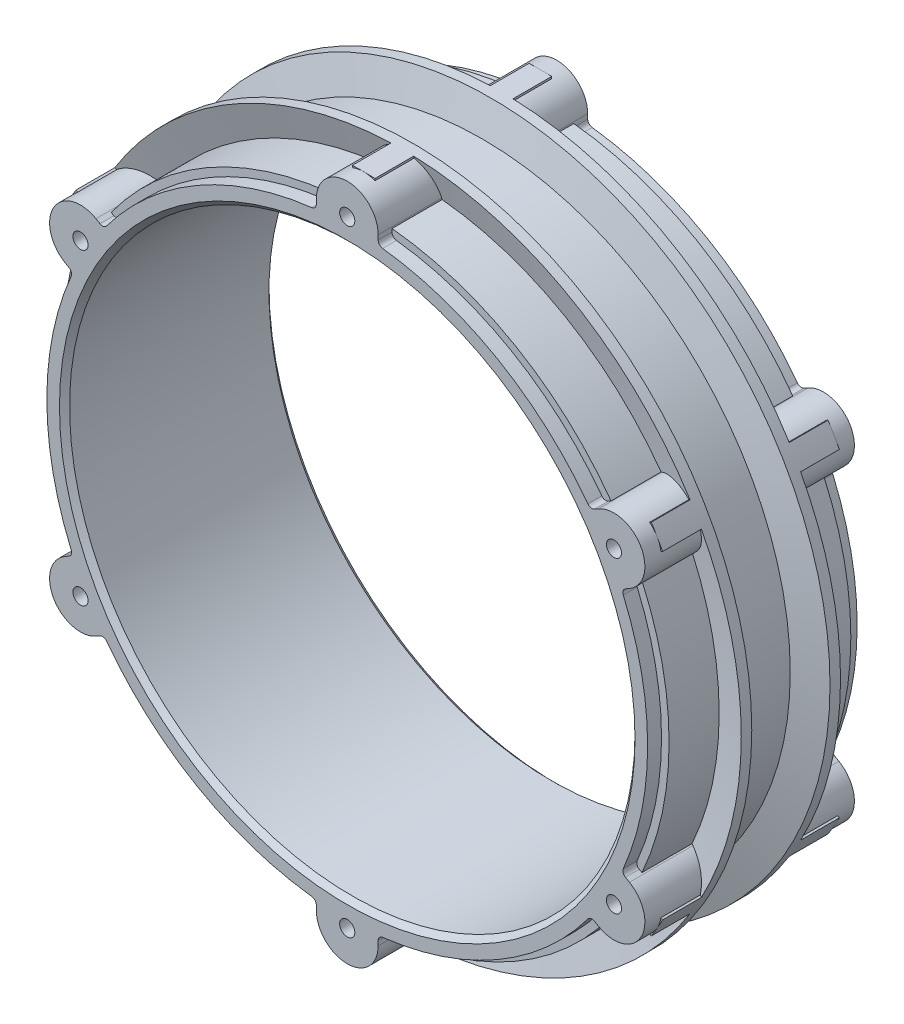
SolidWorks part; units mm, degrees
material "1060 Alloy"
ref_plane "Front Plane" through (0, 0, 0) normal (0, 0, 1) x (1, 0, 0)
ref_plane "Top Plane" through (0, 0, 0) normal (0, 1, 0) x (1, 0, 0)
ref_plane "Right Plane" through (0, 0, 0) normal (1, 0, 0) x (0, 0, -1)
sketch "Sketch1" plane through (0, 0, 0) normal (0, 0, 1) x (1, 0, 0)
  line L0 (6.125, 61) -> (6.125, 60.079)
  line L1 (-6.125, 61) -> (-6.125, 60.079)
  line L2 (55.89, 25.1956) -> (55.0924, 24.7351)
  line L3 (49.765, 35.8044) -> (48.9674, 35.3439)
  line L4 (49.765, -35.8044) -> (48.9674, -35.3439)
  line L5 (55.89, -25.1956) -> (55.0924, -24.7351)
  line L6 (-6.125, -61) -> (-6.125, -60.079)
  line L7 (6.125, -61) -> (6.125, -60.079)
  line L8 (-55.89, -25.1956) -> (-55.0924, -24.7351)
  line L9 (-49.765, -35.8044) -> (-48.9674, -35.3439)
  line L10 (-49.765, 35.8044) -> (-48.9674, 35.3439)
  line L11 (-55.89, 25.1956) -> (-55.0924, 24.7351)
  line L12 (0, 0) -> (7.0072, 59.0859) construction
  arc A0 (-7.0072, 59.0859) -> (7.0072, 59.0859) centre (0, 0) ccw
  circle A1 centre (0, 0) radius 56
  arc A2 (6.125, 61) -> (-6.125, 61) centre (0, 61) ccw
  arc A3 (55.89, 25.1956) -> (49.765, 35.8044) centre (52.8275, 30.5) ccw
  arc A4 (55.0924, 24.7351) -> (54.6735, 23.4745) centre (55.5924, 23.8691) ccw
  arc A5 (48.9674, 35.3439) -> (47.6663, 35.6114) centre (48.4674, 36.2099) cw
  arc A6 (49.765, -35.8044) -> (55.89, -25.1956) centre (52.8275, -30.5) ccw
  arc A7 (48.9674, -35.3439) -> (47.6663, -35.6114) centre (48.4674, -36.2099) ccw
  arc A8 (6.125, 60.079) -> (7.0072, 59.0859) centre (7.125, 60.079) ccw
  arc A9 (-6.125, 60.079) -> (-7.0072, 59.0859) centre (-7.125, 60.079) cw
  arc A10 (55.0924, -24.7351) -> (54.6735, -23.4745) centre (55.5924, -23.8691) cw
  arc A11 (-6.125, -61) -> (6.125, -61) centre (0, -61) ccw
  arc A12 (-6.125, -60.079) -> (-7.0072, -59.0859) centre (-7.125, -60.079) ccw
  arc A13 (6.125, -60.079) -> (7.0072, -59.0859) centre (7.125, -60.079) cw
  arc A14 (-55.89, -25.1956) -> (-49.765, -35.8044) centre (-52.8275, -30.5) ccw
  arc A15 (-55.0924, -24.7351) -> (-54.6735, -23.4745) centre (-55.5924, -23.8691) ccw
  arc A16 (-48.9674, -35.3439) -> (-47.6663, -35.6114) centre (-48.4674, -36.2099) cw
  arc A17 (-49.765, 35.8044) -> (-55.89, 25.1956) centre (-52.8275, 30.5) ccw
  arc A18 (-48.9674, 35.3439) -> (-47.6663, 35.6114) centre (-48.4674, 36.2099) ccw
  arc A19 (-55.0924, 24.7351) -> (-54.6735, 23.4745) centre (-55.5924, 23.8691) cw
  point P0 (0, 0)
  point P10 (0, 0)
  point P11 (6.125, 59.1839)
  point P39 (0, 0)
  dimension "D1" = 119
  dimension "D2" = 6.125
  dimension "D4" = 112
  dimension "D6" = 1
  dimension "D3" = 61
  dimension "D5" = 6
extrude "Boss-Extrude1" add sketch "Sketch1" along normal mid plane 41.5 contours L3 A5 A0 A4 L2 A3 | L5 A10 A0 A7 L4 A6 | L7 A13 A0 A12 L6 A11 | L9 A16 A0 A15 L8 A14 | L11 A19 A0 A18 L10 A17 | A1 | A0 A8 L0 A2 L1 A9 region at (54.3288, 31.3668, 0) region at (-54.3288, 31.3668, 0) region at (54.3288, -31.3668, 0) region at (-54.3288, -31.3668, 0) region at (0, -62.7335, 0)
sketch "Sketch4" plane through (0, 0, 0) normal (0, 0, 1) x (1, 0, 0)
  circle A0 centre (0, 0) radius 61
  circle A1 centre (0, 0) radius 59.5
  arc A4 (-7.0072, 59.0859) -> (-47.6663, 35.6114) centre (0, 0) ccw construction
  dimension "D1" = 122
extrude "Boss-Extrude2" add sketch "Sketch4" along normal mid plane 36 contours A0 A1 region at (-60.8275, 0, 0)
sketch "Sketch3" plane through (0, 0, 20.75) normal (0, 0, -1) x (-1, 0, 0)
  circle A0 centre (0, 61) radius 1.5
  dimension "D1" = 3
extrude "Cut-Extrude1" cut sketch "Sketch3" along normal blind 6
pattern_circular "CirPattern1" count 6 over 360 about axis through (0, 0, 20.75) along (0, 0, 1) of "Cut-Extrude1"
mirror "Mirror1" about plane through (0, 0, 0) normal (0, 0, 1) of "Cut-Extrude1", "CirPattern1"
sketch "Sketch5" plane through (0, 0, 0) normal (0, 1, 0) x (0, 0, -1)
  line L0 (-6, 61) -> (0, 61) construction
  line L1 (-12.08, 75) -> (-10, 75)
  line L2 (-6, 61) -> (-10, 75)
  line L4 (-12.08, 75) -> (-8.08, 61)
  line L5 (18, 61) -> (-18, 61) construction
  line L6 (-8.08, 61) -> (-6, 61)
  line L8 (0, 0) -> (0, 50000) construction
  line L9 (10, 75) -> (6, 61)
  line L10 (8.08, 61) -> (6, 61)
  line L11 (12.08, 75) -> (8.08, 61)
  line L12 (12.08, 75) -> (10, 75)
  line L13 (0, 0) -> (-142.6221, 0) construction
  point P16 (-10, 74.8399)
  dimension "D1" = 2
  dimension "D2" = 6
  dimension "D3" = 10
  dimension "D4" = 14
revolve "Revolve1" add sketch "Sketch5" angle 360 about L13
sketch "Sketch7" plane through (0, 0, 0) normal (0, 0, 1) x (1, 0, 0)
  line L1 (-2.25, 74.9662) -> (2.25, 74.9662)
  line L2 (-2.25, 74.9662) -> (-2.25, 66.6968)
  line L3 (-2.25, 66.6968) -> (2.25, 66.6968)
  line L4 (2.25, 74.9662) -> (2.25, 66.6968)
  circle A0 centre (0, 0) radius 75 construction
  arc A1 (6.125, 61) -> (-6.125, 61) centre (0, 61) ccw construction
  arc A2 (6.125, 61) -> (-6.125, 61) centre (0, 61) ccw construction
  point P9 (2.6225, 66.5352)
  point P10 (-2.2153, 66.7103)
  dimension "D1" = 4.5
extrude "Boss-Extrude3" add sketch "Sketch7" along normal mid plane 35
pattern_circular "CirPattern2" count 6 over 360 about axis through (0, 0, 20.75) along (0, 0, 1) of "Boss-Extrude3"
sketch "Sketch6" plane through (0, 0, 0) normal (0, 1, 0) x (1, 0, 0)
  line L0 (-61, -6) -> (-61, 6)
  line L1 (-61, 6) -> (-61, -6) construction
  line L2 (-75, 10) -> (-61, 6)
  line L3 (-61, -6) -> (-75, -10)
  line L4 (-75, -10) -> (-75, 10)
  line L7 (0, 0) -> (0, 50000) construction
  line L8 (-61, -6) -> (-75, -10) construction
  line L9 (-75, -10) -> (-66.0477, -10) construction
  line L10 (51.3275, -20.75) -> (54.3275, -20.75) construction
  line L11 (-75, -20.75) -> (-67.125, -20.75)
  line L12 (-75, -20.75) -> (-75, 20.75)
  line L13 (-75, 20.75) -> (-67.125, 20.75)
  line L14 (-67.125, -20.75) -> (-67.125, 20.75)
  line L15 (54.3275, 20.75) -> (51.3275, 20.75) construction
  dimension "D1" = 6.125
revolve "Cut-Revolve1" cut sketch "Sketch6" angle 360 about L7 region at (-64.1924, 0, 0) region at (-70.9382, 0, 14.7947) region at (-71.2289, 0, 0) region at (-70.9382, 0, -14.7947)
chamfer "Chamfer1" distance 1 angle 45 2 edges at (56, 0, -20.75) (56, 0, 20.75)
